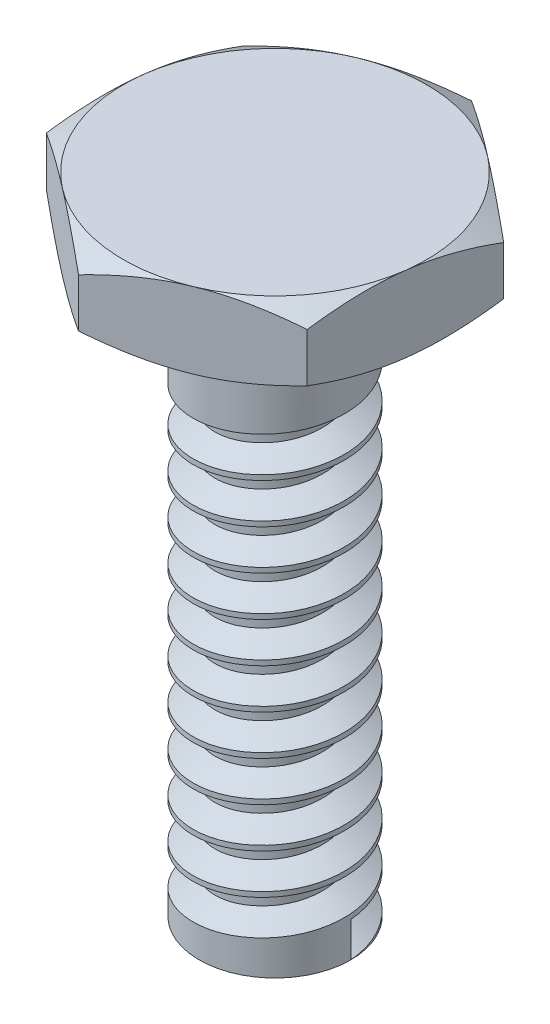
SolidWorks part; units mm, degrees
material "Stal nierdzewna (ferrytyczna)"
ref_plane "Front Plane" through (0, 0, 0) normal (0, 0, 1) x (1, 0, 0)
ref_plane "Top Plane" through (0, 0, 0) normal (0, 1, 0) x (1, 0, 0)
ref_plane "Right Plane" through (0, 0, 0) normal (1, 0, 0) x (0, 0, -1)
sketch "Szkic1" plane through (0, 0, 0) normal (0, 1, 0) x (1, 0, 0)
  circle A0 centre (0, 0) radius 2
extrude "Dodanie-wyciągnięcie1" add sketch "Szkic1" along normal blind 15
sketch "Szkic2" plane through (0, 15, 0) normal (0, 1, 0) x (1, 0, 0)
  line L1 (4.2679, 1.766) -> (0.6045, 4.5791)
  line L2 (0.6045, 4.5791) -> (-3.6633, 2.8131)
  line L3 (-3.6633, 2.8131) -> (-4.2679, -1.766)
  line L4 (-4.2679, -1.766) -> (-0.6045, -4.5791)
  line L5 (-0.6045, -4.5791) -> (3.6633, -2.8131)
  line L6 (3.6633, -2.8131) -> (4.2679, 1.766)
  circle A0 centre (0, 0) radius 4 construction
extrude "Dodanie-wyciągnięcie2" add sketch "Szkic2" along normal blind 2
sketch "Szkic3" plane through (0, 17, 0) normal (0, 1, 0) x (1, 0, 0)
  circle A0 centre (0, 0) radius 4
extrude "Wytnij-wyciągnięcie1" cut sketch "Szkic3" against normal blind 2 draft 60 flip side to cut
sketch "Szkic4" plane through (0, 15, 0) normal (0, -1, 0) x (1, 0, 0)
  circle A0 centre (0, 0) radius 4
extrude "Wytnij-wyciągnięcie2" cut sketch "Szkic4" against normal blind 2 draft 60 flip side to cut
thread "Gwint1" pitch 1.0583 method cut profile "Profil gwintu1" start angle 0, offset 0, length 12, pitch 1.0583, diameter 4
ref_plane "Płaszczyzna1" through (2, 0, 0) normal (0, 0, 1) x (1, 0, 0)
sketch "Profil gwintu1" plane through (2, 0, 0) normal (0, 0, 1) x (1, 0, 0)
  line L0 (0, 0) -> (0, 1.0583) construction
  line L11 (0, 0) -> (0, 0.926)
  line L12 (0, 0.926) -> (-0.5728, 0.5953)
  line L13 (-0.5728, 0.5953) -> (-0.5728, 0.3307)
  line L15 (-0.5728, 0.3307) -> (0, 0)
  line L17 (-0.5728, 0.463) -> (0, 0.463) construction
  point P2 (0, 0)
  dimension "Pitch" = 1.0583
  dimension "Profile_Angle" = 60
  dimension "Profile_Land" = 0.2646
  dimension "Profile_Height" = 0.5728
